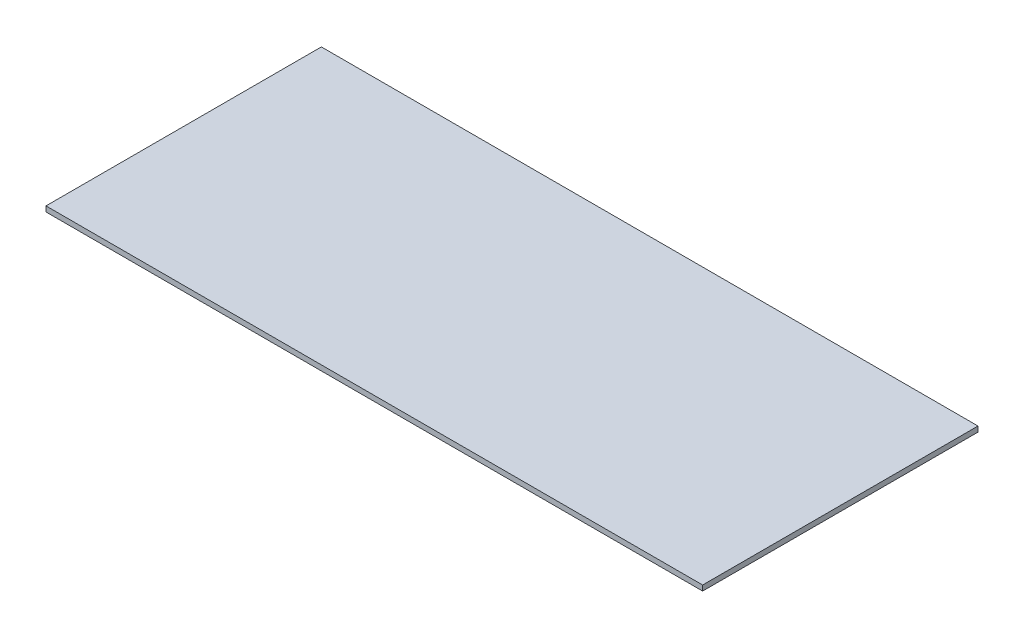
SolidWorks part; units mm, degrees
material "Acrylic (Medium-high impact)"
ref_plane "Front" through (0, 0, 0) normal (0, 0, 1) x (1, 0, 0)
ref_plane "Top" through (0, 0, 0) normal (0, 1, 0) x (1, 0, 0)
ref_plane "Right" through (0, 0, 0) normal (1, 0, 0) x (0, 0, -1)
sketch "Sketch1" plane through (0, 0, 0) normal (0, 1, 0) x (1, 0, 0)
  line L1 (-196.85, -82.55) -> (196.85, -82.55)
  line L2 (-196.85, -82.55) -> (-196.85, 82.55)
  line L3 (-196.85, 82.55) -> (196.85, 82.55)
  line L4 (196.85, -82.55) -> (196.85, 82.55)
  line L5 (-196.85, -82.55) -> (196.85, 82.55) construction
  line L6 (-196.85, 82.55) -> (196.85, -82.55) construction
  point P0 (0, 0)
  dimension "D1" = 165.1
  dimension "D2" = 393.7
extrude "Boss-Extrude1" add sketch "Sketch1" along normal blind 3.175
